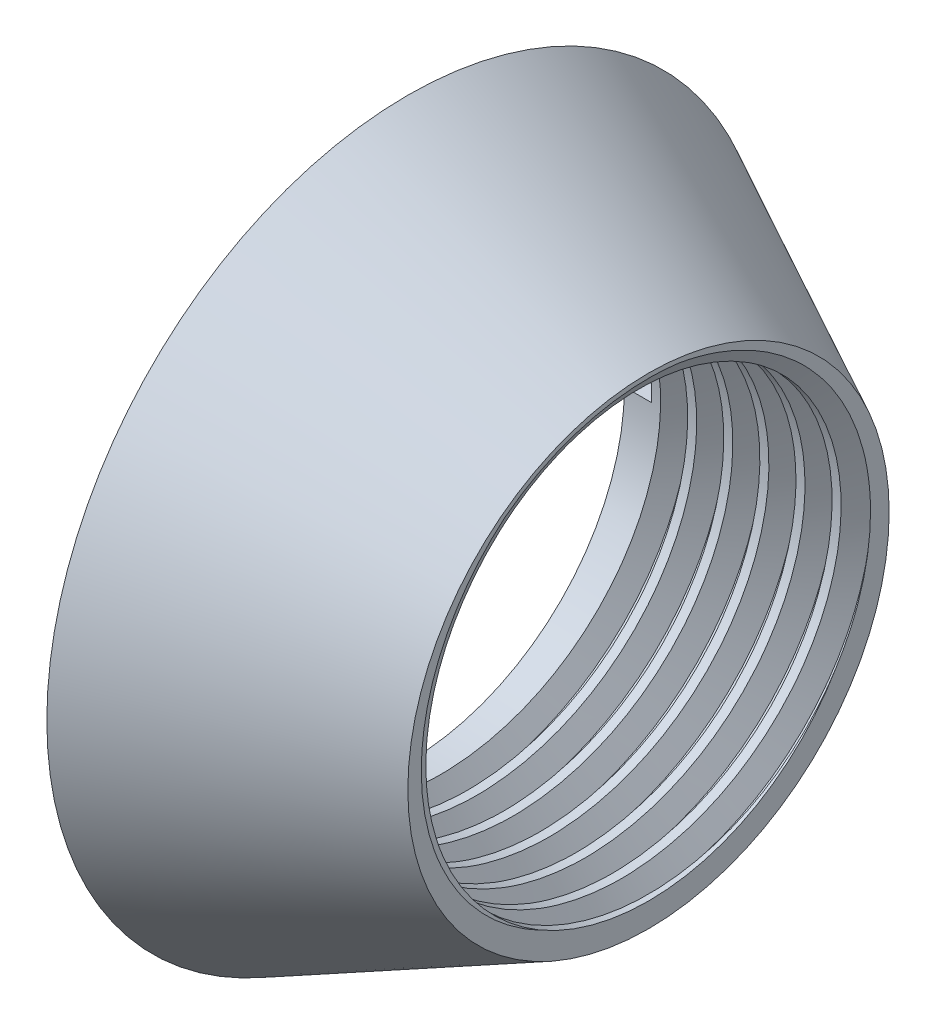
SolidWorks part; units mm, degrees
ref_plane "Plano frontal" through (0, 0, 0) normal (0, 0, 1) x (1, 0, 0)
ref_plane "Plano superior" through (0, 0, 0) normal (0, 1, 0) x (1, 0, 0)
ref_plane "Plano direito" through (0, 0, 0) normal (1, 0, 0) x (0, 0, -1)
sketch "Esboço1" plane through (0, 0, 0) normal (1, 0, 0) x (0, 0, -1)
  circle A0 centre (0, 0) radius 30
  dimension "D1" = 60
ref_plane "Plano1" through (20, 0, 0) normal (1, 0, 0) x (0, 0, -1)
sketch "Esboço2" plane through (20, 0, 0) normal (1, 0, 0) x (0, 0, -1)
  circle A0 centre (0, 0) radius 20
  dimension "D1" = 40
loft "Loft1" add profiles "Esboço2", "Esboço1" connector at (20, 7.0225, 18.7266) connector at (0, 13.7371, 26.67)
sketch "Esboço3" plane through (20, 0, 0) normal (1, 0, 0) x (0, 0, -1)
  circle A0 centre (0, 0) radius 18
  dimension "D1" = 36
extrude "Corte-extrusão1" cut sketch "Esboço3" against normal through all
thread "Rosca1" pitch 3 method cut profile "Perfil da rosca1" start angle 0, offset 0, length 0, pitch 3, diameter 36
ref_plane "Plano2" through (0, 0, -18) normal (0, -1, 0) x (0, 0, -1)
sketch "Perfil da rosca1" plane through (0, 0, -18) normal (0, -1, 0) x (0, 0, -1)
  line L0 (0, 0) -> (0, 3) construction
  line L1 (0, 0) -> (1.6238, 0.9375)
  line L2 (1.6238, 0.9375) -> (1.6238, 1.3125)
  line L3 (1.6238, 1.3125) -> (0, 2.25)
  line L4 (1.6238, 1.125) -> (0, 1.125) construction
  line L11 (0, 0) -> (0, 2.25)
  point P2 (0, 0)
  dimension "Pitch" = 3
  dimension "Profile_Angle" = 60
  dimension "Profile_Land" = 0.375
  dimension "Profile_Height" = 1.6238
